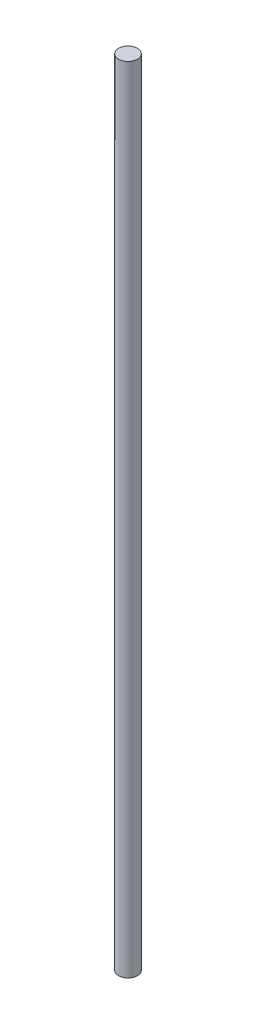
SolidWorks part; units mm, degrees
ref_plane "Front Plane" through (0, 0, 0) normal (0, 0, 1) x (1, 0, 0)
ref_plane "Top Plane" through (0, 0, 0) normal (0, 1, 0) x (1, 0, 0)
ref_plane "Right Plane" through (0, 0, 0) normal (1, 0, 0) x (0, 0, -1)
sketch "Sketch2" plane through (0, 0, 0) normal (0, 1, 0) x (1, 0, 0)
  circle A0 centre (0, 0) radius 5
  dimension "D1" = 10
extrude "Boss-Extrude1" add sketch "Sketch2" along normal blind 420
